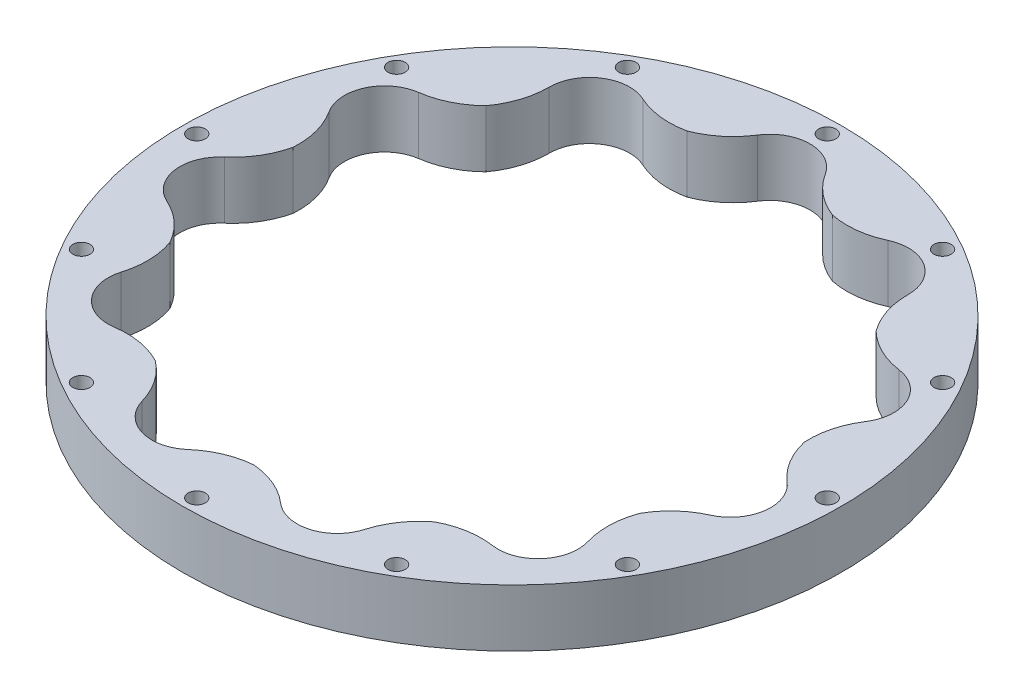
SolidWorks part; units mm, degrees
ref_plane "Front Plane" through (0, 0, 0) normal (0, 0, 1) x (1, 0, 0)
ref_plane "Top Plane" through (0, 0, 0) normal (0, 1, 0) x (1, 0, 0)
ref_plane "Right Plane" through (0, 0, 0) normal (1, 0, 0) x (0, 0, -1)
sketch "Sketch1" plane through (0, 0, 0) normal (0, 1, 0) x (1, 0, 0)
  circle A0 centre (0, 0) radius 45
  circle A1 centre (0, 45) radius 7
  circle A2 centre (24.3288, 37.8564) radius 7
  circle A3 centre (40.9334, 18.6937) radius 7
  circle A4 centre (44.542, -6.4042) radius 7
  circle A5 centre (34.0087, -29.4687) radius 7
  circle A6 centre (12.678, -43.1772) radius 7
  circle A7 centre (-12.678, -43.1772) radius 7
  circle A8 centre (-34.0087, -29.4687) radius 7
  circle A9 centre (-44.542, -6.4042) radius 7
  circle A10 centre (-40.9334, 18.6937) radius 7
  circle A11 centre (-24.3288, 37.8564) radius 7
  circle A12 centre (0, 0) radius 57.5
  circle A13 centre (0, 0) radius 55 construction
  circle A14 centre (0, 55) radius 1.5
  circle A15 centre (27.5, 47.6314) radius 1.5
  circle A16 centre (47.6314, 27.5) radius 1.5
  circle A17 centre (55, 0) radius 1.5
  circle A18 centre (47.6314, -27.5) radius 1.5
  circle A19 centre (27.5, -47.6314) radius 1.5
  circle A20 centre (0, -55) radius 1.5
  circle A21 centre (-27.5, -47.6314) radius 1.5
  circle A22 centre (-47.6314, -27.5) radius 1.5
  circle A23 centre (-55, 0) radius 1.5
  circle A24 centre (-47.6314, 27.5) radius 1.5
  circle A25 centre (-27.5, 47.6314) radius 1.5
  point P27 (0, 0)
  point P54 (0, 0)
  dimension "D1" = 90
  dimension "D2" = 14
  dimension "D4" = 115
  dimension "D5" = 110
  dimension "D6" = 3
  dimension "D3" = 11
  dimension "D7" = 12
extrude "Boss-Extrude1" add sketch "Sketch1" along normal blind 10 contours A12 A25 A24 A23 A22 A21 A20 A19 A18 A17 A16 A15 A14 A11 A0 A1 A2 A3 A4 A5 A6 A7 A8 A9 A10 region at (-57.3374, 0, 0)
fillet "Fillet1" radius 14 22 edges at (44.9962, 5, -0.5811) (43.3373, 5, -12.1194) (38.1674, 5, 23.838) (43.0099, 5, 13.2344) (29.0271, 5, 34.3864) (19.2207, 5, 40.6886) (5.8285, 5, 44.6209) (-5.8285, 5, 44.6209) (-19.2207, 5, 40.6886) (-29.0271, 5, 34.3864) (-43.0099, 5, 13.2344) (-38.1674, 5, 23.838) (-44.9962, 5, -0.5811) (-43.3373, 5, -12.1194) (-37.5391, 5, -24.8156) (-29.9054, 5, -33.6254) (37.5391, 5, -24.8156) (29.9054, 5, -33.6254) (18.1636, 5, -41.1714) (6.9788, 5, -44.4556) (-6.9788, 5, -44.4556) (-18.1636, 5, -41.1714)
